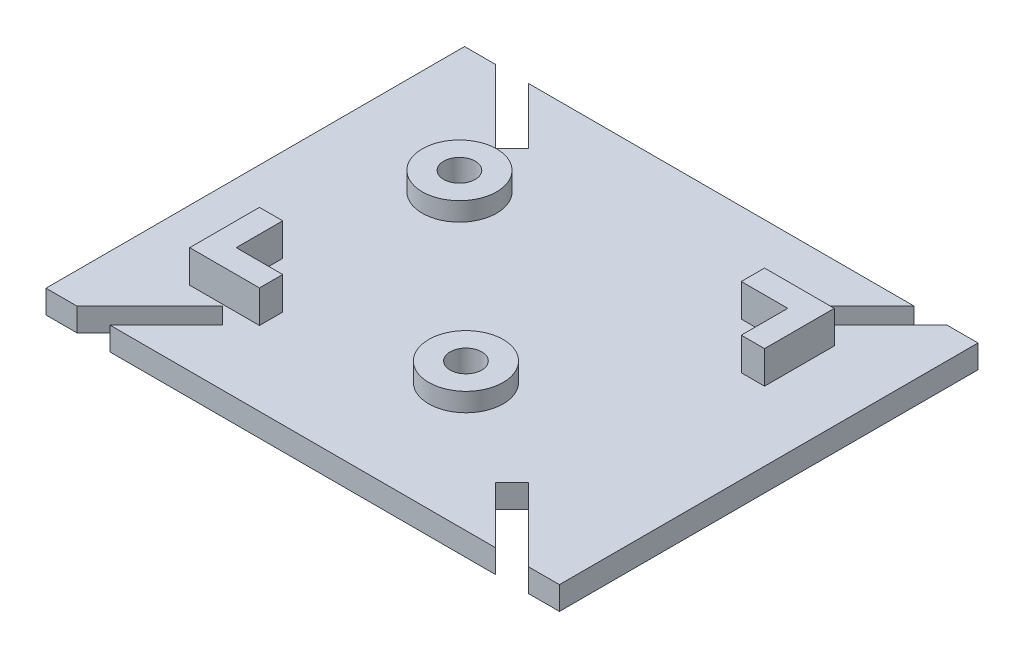
SolidWorks part; units mm, degrees
ref_plane "Front" through (0, 0, 0) normal (0, 0, 1) x (1, 0, 0)
ref_plane "Top" through (0, 0, 0) normal (0, 1, 0) x (1, 0, 0)
ref_plane "Right" through (0, 0, 0) normal (1, 0, 0) x (0, 0, -1)
sketch "Sketch3" plane through (0, 0, 0) normal (0, 1, 0) x (1, 0, 0)
  line L1 (-27.6, -22.5) -> (27.6, -22.5)
  line L2 (-27.6, -22.5) -> (-27.6, 22.5)
  line L3 (-27.6, 22.5) -> (27.6, 22.5)
  line L4 (27.6, -22.5) -> (27.6, 22.5)
  line L5 (-27.6, -22.5) -> (27.6, 22.5) construction
  line L6 (-27.6, 22.5) -> (27.6, -22.5) construction
  point P0 (0, 0)
  dimension "D1" = 45
  dimension "D2" = 55.2
extrude "Boss-Extrude1" add sketch "Sketch3" along normal mid plane 2.5
sketch "Sketch4" plane through (0, 1.25, 0) normal (0, 1, 0) x (1, 0, 0)
  line L0 (-14.35, 8.7) -> (-17.65, 8.7) construction
  line L1 (-17.65, -12) -> (17.65, -12) construction
  line L2 (-17.65, -12) -> (-17.65, 12) construction
  line L3 (-17.65, 12) -> (17.65, 12) construction
  line L4 (17.65, -12) -> (17.65, 12) construction
  line L5 (-17.65, -12) -> (17.65, 12) construction
  line L6 (-17.65, 12) -> (17.65, -12) construction
  line L7 (-14.35, 8.7) -> (-14.35, 12) construction
  line L8 (3.75, -8.7) -> (3.75, -12) construction
  circle A0 centre (-14.35, 8.7) radius 4
  circle A1 centre (3.75, -8.7) radius 4
  point P0 (0, 0)
  point P6 (-14.35, 8.7)
  point P7 (3.75, -8.7)
  dimension "D5" = 8
  dimension "D1" = 24
  dimension "D2" = 35.3
  dimension "D3" = 3.3
  dimension "D4" = 21.4
extrude "Boss-Extrude2" add sketch "Sketch4" along normal blind 2
hole_wizard "M3 Clearance Hole1" positions "Sketch5" profile "Sketch6" hole size "M3" standard "ANSI Metric" end condition through all
sketch "Sketch5" plane through (0, 3.25, 0) normal (0, 1, 0) x (1, 0, 0)
  point P0 (-14.35, 8.7)
  point P3 (3.75, -8.7)
sketch "Sketch6" plane through (-14.35, 3.25, -8.7) normal (1, 0, 0) x (0, 0, 1)
  line L0 (0, 0) -> (0, 4.5)
  line L1 (0, 4.5) -> (1.7, 4.5)
  line L2 (1.7, 4.5) -> (1.7, 0)
  line L5 (1.7, 0) -> (0, 0)
  line L11 (0, -6.35) -> (0, 107.95) construction
  dimension "Thru Hole Dia." = 3.4
  dimension "Thru Hole Depth" = 4.5
sketch "Sketch7" plane through (0, 1.25, 0) normal (0, 1, 0) x (1, 0, 0)
  line L0 (-17.65, -12) -> (-17.65, -7)
  line L1 (-17.65, -12) -> (-17.65, 12) construction
  line L2 (-17.65, -7) -> (-20.15, -7)
  line L3 (-20.15, -7) -> (-20.15, -14.5)
  line L4 (-20.15, -14.5) -> (-12.65, -14.5)
  line L5 (-12.65, -14.5) -> (-12.65, -12)
  line L6 (-17.65, -12) -> (17.65, -12) construction
  line L7 (-12.65, -12) -> (-17.65, -12)
  line L8 (17.65, 12) -> (12.65, 12)
  line L9 (-17.65, 12) -> (17.65, 12) construction
  line L10 (12.65, 12) -> (12.65, 14.5)
  line L11 (12.65, 14.5) -> (20.15, 14.5)
  line L12 (20.15, 14.5) -> (20.15, 7)
  line L13 (20.15, 7) -> (17.65, 7)
  line L14 (17.65, -12) -> (17.65, 12) construction
  line L15 (17.65, 7) -> (17.65, 12)
  dimension "D1" = 5
  dimension "D2" = 2.5
extrude "Boss-Extrude3" add sketch "Sketch7" along normal blind 3.5
sketch "Sketch8" plane through (0, 1.25, 0) normal (0, 1, 0) x (1, 0, 0)
  line L0 (-22.5, -22.5) -> (22.5, 22.5) construction
  line L1 (-22.5, 22.5) -> (22.5, -22.5) construction
  line L2 (0, 0) -> (0, 22.5) construction
  line L3 (27.6, 22.5) -> (-27.6, 22.5) construction
  line L4 (-30.3275, 28.5598) -> (-16.4402, 14.6725)
  line L5 (-30.3275, 28.5598) -> (-28.5598, 30.3275)
  line L6 (-16.4402, 14.6725) -> (-14.6725, 16.4402)
  line L7 (-28.5598, 30.3275) -> (-14.6725, 16.4402)
  line L8 (-30.3275, 28.5598) -> (-14.6725, 16.4402) construction
  line L9 (-16.4402, 14.6725) -> (-28.5598, 30.3275) construction
  point P4 (0, 0)
  point P7 (0, 0)
  point P16 (-22.5, 22.5)
  dimension "D4" = 22
  dimension "D1" = 45
  dimension "D2" = 45
  dimension "D3" = 2.5
extrude "Cut-Extrude1" cut sketch "Sketch8" against normal through all and the other way through all
ref_axis "Axis1" through (0, 50, 0) along (0, -1, 0)
pattern_circular "CirPattern1" count 4 over 360 about axis through (0, 50, 0) along (0, -1, 0) of "Cut-Extrude1"
